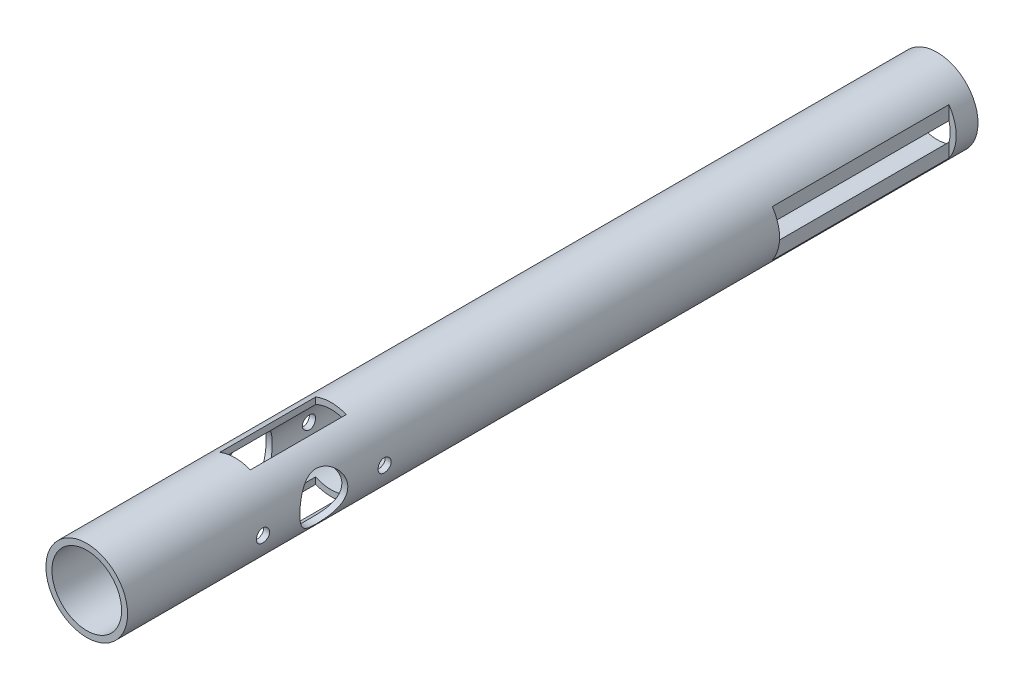
SolidWorks part; units mm, degrees
material "A-Glass Fiber"
ref_plane "Front" through (0, 0, 0) normal (0, 0, 1) x (1, 0, 0)
ref_plane "Top" through (0, 0, 0) normal (0, 1, 0) x (1, 0, 0)
ref_plane "Right" through (0, 0, 0) normal (1, 0, 0) x (0, 0, -1)
sketch "Sketch1" plane through (0, 0, 0) normal (0, 0, 1) x (1, 0, 0)
  circle A0 centre (0, 0) radius 9.36
  circle A1 centre (0, 0) radius 7.99
  dimension "D1" = 18.72
  dimension "D2" = 15.98
extrude "Extrude1" add sketch "Sketch1" along normal blind 195
sketch "Sketch2" plane through (0, 0, 0) normal (1, 0, 0) x (0, 0, -1)
  line L0 (-30, -47.5362) -> (-30, 39.1475) construction
  line L1 (0, -9.36) -> (0, 9.36) construction
  line L2 (-150, -93.5027) -> (-150, 51.4365) construction
  line L3 (-195, 9.36) -> (-195, -9.36) construction
  circle A0 centre (-30, 0) radius 1.5
  circle A1 centre (-150, 0) radius 5.5
  circle A2 centre (-136.0625, 0) radius 1.5
  circle A3 centre (-163.9375, 0) radius 1.5
  point P10 (-163.9375, 0)
  point P11 (-136.0625, 0)
  point P16 (-195, 0)
  dimension "D2" = 150
  dimension "D3" = 13.9375
  dimension "D5" = 31.0625
  dimension "D6" = 11
  dimension "D7" = 3
  dimension "D1" = 30
  dimension "D4" = 13.9375
extrude "Extrude2" cut sketch "Sketch2" against normal through all and the other way through all
sketch "Sketch3" plane through (0, 0, 0) normal (0, 1, 0) x (1, 0, 0)
  line L0 (-54.8402, -150) -> (72.4613, -150) construction
  line L1 (7.99, 0) -> (-7.99, 0) construction
  line L2 (-44.3384, -139) -> (38.4408, -139) construction
  line L3 (-76.6388, -161) -> (67.6466, -161) construction
  line L4 (3.5, -160.8387) -> (3.5, -87.3966) construction
  line L5 (0, -179.9469) -> (0, -88.7091) construction
  line L6 (-3.5, -169.4108) -> (-3.5, -98.3485) construction
  line L7 (14.05, -5) -> (7.7, -5)
  line L8 (-3.5, -139) -> (3.5, -139)
  line L9 (-3.5, -139) -> (-3.5, -161)
  line L10 (-3.5, -161) -> (3.5, -161)
  line L11 (3.5, -139) -> (3.5, -161)
  line L12 (7.7, -5) -> (7.7, -45.5)
  line L13 (7.7, -45.5) -> (14.05, -45.5)
  line L14 (14.05, -45.5) -> (14.05, -5)
  dimension "D1" = 150
  dimension "D2" = 11
  dimension "D3" = 22
  dimension "D4" = 3.5
  dimension "D5" = 7
  dimension "D6" = 6.35
  dimension "D7" = 40.5
  dimension "D8" = 7.7
  dimension "D9" = 5
extrude "Extrude3" cut sketch "Sketch3" against normal blind 25 and the other way blind 25
